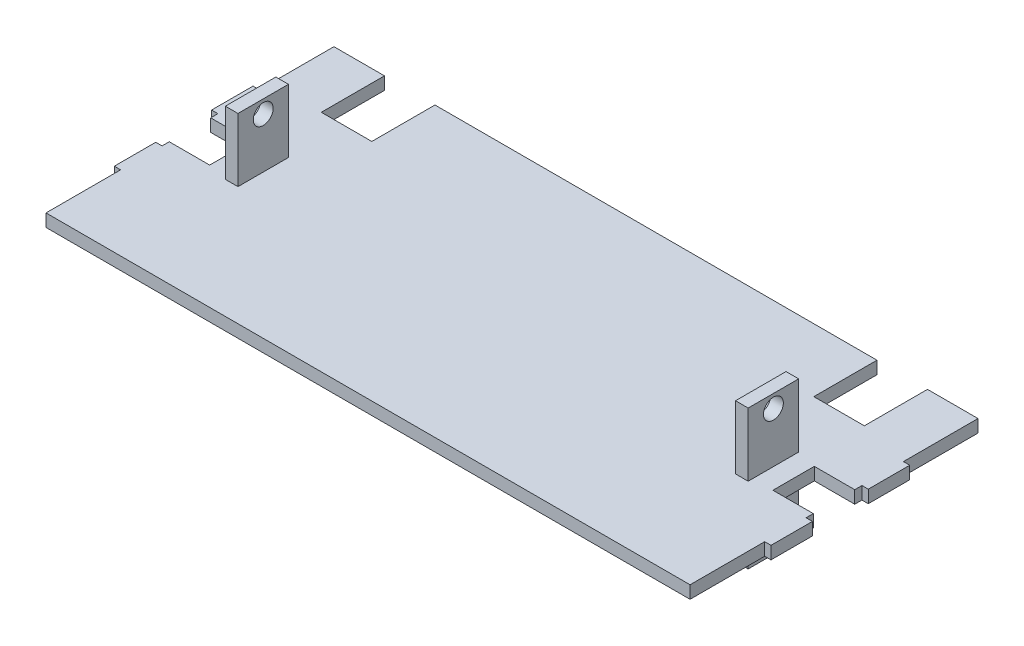
SolidWorks part; units mm, degrees
ref_plane "Front Plane" through (0, 0, 0) normal (0, 0, 1) x (1, 0, 0)
ref_plane "Top Plane" through (0, 0, 0) normal (0, 1, 0) x (1, 0, 0)
ref_plane "Right Plane" through (0, 0, 0) normal (1, 0, 0) x (0, 0, -1)
sketch "Sketch1" plane through (0, 0, 0) normal (0, 1, 0) x (1, 0, 0)
  line L0 (0, 72.39) -> (0, -72.39) construction
  line L1 (161.925, -72.39) -> (-161.925, -72.39)
  line L2 (161.925, -72.39) -> (161.925, -34.8747)
  line L3 (161.925, 72.39) -> (136.525, 72.39)
  line L4 (-161.925, -72.39) -> (-161.925, -34.8747)
  line L5 (161.925, -72.39) -> (-161.925, 72.39) construction
  line L6 (161.925, 72.39) -> (-161.925, -72.39) construction
  line L7 (161.925, 10.414) -> (141.605, 10.414)
  line L9 (161.925, -10.414) -> (141.605, -10.414)
  line L10 (141.605, 10.414) -> (141.605, -10.414)
  line L11 (-136.525, 72.39) -> (-161.925, 72.39)
  line L13 (-161.925, -10.414) -> (-141.605, -10.414)
  line L14 (-141.605, 10.414) -> (-141.605, -10.414)
  line L15 (-161.925, 10.414) -> (-141.605, 10.414)
  line L17 (-127, 0) -> (127, 0) construction
  line L18 (-161.925, 14.0467) -> (-165.1, 14.0467)
  line L20 (-161.925, 34.8747) -> (-165.1, 34.8747)
  line L21 (-165.1, 14.0467) -> (-165.1, 34.8747)
  line L22 (-161.925, -34.8747) -> (-165.1, -34.8747)
  line L23 (-165.1, -14.0467) -> (-165.1, -34.8747)
  line L24 (-161.925, -14.0467) -> (-165.1, -14.0467)
  line L27 (161.925, -14.0467) -> (165.1, -14.0467)
  line L28 (165.1, -14.0467) -> (165.1, -34.8747)
  line L29 (161.925, -34.8747) -> (165.1, -34.8747)
  line L30 (161.925, 34.8747) -> (165.1, 34.8747)
  line L31 (165.1, 14.0467) -> (165.1, 34.8747)
  line L32 (161.925, 14.0467) -> (165.1, 14.0467)
  line L34 (-161.925, 34.8747) -> (-161.925, 72.39)
  line L35 (-161.925, -14.0467) -> (-161.925, -10.414)
  line L36 (161.925, 34.8747) -> (161.925, 72.39)
  line L37 (161.925, -14.0467) -> (161.925, -10.414)
  line L38 (-161.925, 10.414) -> (-161.925, 14.0467)
  line L39 (161.925, 10.414) -> (161.925, 14.0467)
  line L40 (-136.525, 72.39) -> (-136.525, 40.64)
  line L41 (-136.525, 40.64) -> (-111.125, 40.64)
  line L42 (-111.125, 72.39) -> (-111.125, 40.64)
  line L44 (111.125, 72.39) -> (111.125, 40.64)
  line L45 (111.125, 40.64) -> (136.525, 40.64)
  line L46 (136.525, 72.39) -> (136.525, 40.64)
  line L47 (111.125, 72.39) -> (-111.125, 72.39)
  point P0 (0, 0)
  point P6 (127, 0)
  dimension "D1" = 323.85
  dimension "D2" = 144.78
  dimension "D3" = 20.828
  dimension "D5" = 3.175
  dimension "D6" = 20.828
  dimension "D4" = 20.32
  dimension "D7" = 31.75
  dimension "D8" = 25.4
  dimension "D9" = 25.4
  dimension "D10" = 31.75
  dimension "D12" = 25.4
  dimension "D11" = 25.4
extrude "Boss-Extrude1" add sketch "Sketch1" along normal mid plane 6.35
sketch "Sketch2" plane through (0, 0, 0) normal (0, 1, 0) x (1, 0, 0)
  line L0 (-141.605, 10.414) -> (-141.605, -10.414) construction
  line L1 (125.095, -12.7) -> (131.445, -12.7)
  line L2 (125.095, -12.7) -> (125.095, 12.7)
  line L3 (125.095, 12.7) -> (131.445, 12.7)
  line L4 (131.445, -12.7) -> (131.445, 12.7)
  line L5 (125.095, -12.7) -> (131.445, 12.7) construction
  line L6 (125.095, 12.7) -> (131.445, -12.7) construction
  line L9 (-125.095, -12.7) -> (-125.095, 12.7)
  line L10 (-125.095, 12.7) -> (-131.445, 12.7)
  line L11 (-131.445, -12.7) -> (-131.445, 12.7)
  line L12 (-125.095, -12.7) -> (-131.445, -12.7)
  line L13 (141.605, -10.414) -> (141.605, 10.414) construction
  point P0 (128.27, 0)
  point P10 (141.605, 0)
  dimension "D1" = 10.16
  dimension "D2" = 10.16
  dimension "D3" = 25.4
  dimension "D4" = 25.4
  dimension "D5" = 6.35
  dimension "D6" = 6.35
  dimension "D7" = 6.35
extrude "Boss-Extrude2" add sketch "Sketch2" along normal mid plane 70.104
sketch "Sketch3" plane through (-131.445, 0, 0) normal (-1, 0, 0) x (0, 0, 1)
  circle A0 centre (0, 28.4406) radius 5.0038
  circle A1 centre (0, -28.4406) radius 5.0038
  dimension "D1" = 10.0076
  dimension "D2" = 10.0076
extrude "Cut-Extrude1" cut sketch "Sketch3" against normal through all both and the other way through all
equation "\"length\"=12.75"
equation "\"width\"= 5.7"
equation "\"height\"= 0.25"
equation "\"D1@Sketch1\"=\"length\""
equation "\"D2@Sketch1\"=\"width\""
equation "\"eyebolt width\"= 0.82"
equation "\"eyebolt length\"= 0.8"
equation "\"D3@Sketch1\"=\"eyebolt width\""
equation "\"D4@Sketch1\"=\"eyebolt length\""
equation "\"lead screw holder height\"= 2.76"
equation "\"lead screw diameter\"=0.394"
equation "\"D1@Sketch3\"=\"lead screw diameter\""
equation "\"distance from holders to board\"=0.4"
equation "\"D2@Sketch3\"=\"lead screw diameter\""
